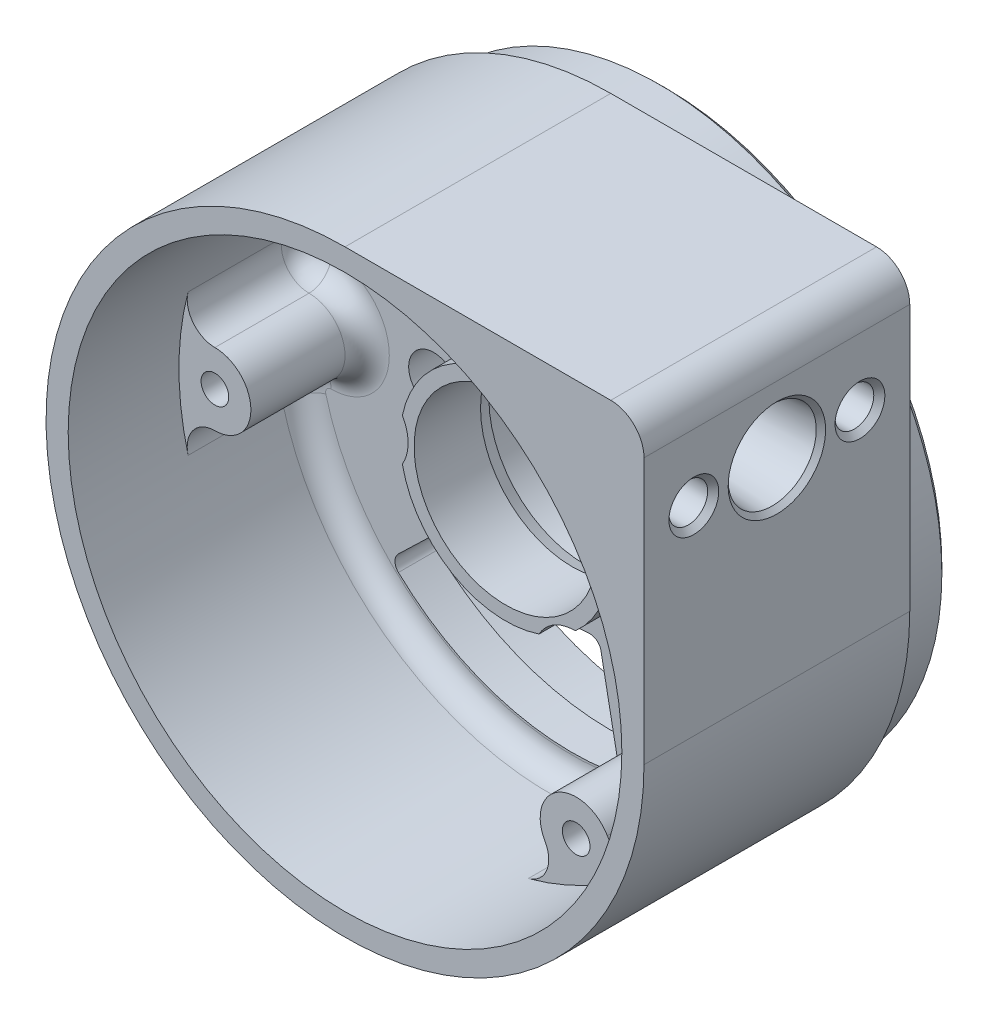
SolidWorks part; units mm, degrees
ref_plane "Front Plane" through (0, 0, 0) normal (0, 0, 1) x (1, 0, 0)
ref_plane "Top Plane" through (0, 0, 0) normal (0, 1, 0) x (1, 0, 0)
ref_plane "Right Plane" through (0, 0, 0) normal (1, 0, 0) x (0, 0, -1)
sketch "Sketch1" plane through (0, 0, 0) normal (0, 0, 1) x (1, 0, 0)
  line L0 (-12.5, 0) -> (0, 0) construction
  line L1 (0, 0) -> (6.25, 10.8253) construction
  line L2 (6.25, -10.8253) -> (0, 0) construction
  circle A0 centre (0, 0) radius 27
  circle A1 centre (0, 0) radius 12.5 construction
  circle A2 centre (0, 0) radius 7.75
  circle A3 centre (0, 0) radius 3 construction
  circle A4 centre (6.25, 10.8253) radius 2.25
  circle A5 centre (-12.5, 0) radius 2.25
  circle A6 centre (6.25, -10.8253) radius 2.25
  dimension "D1" = 54
  dimension "D2" = 6
  dimension "D3" = 15.5
  dimension "D4" = 25
  dimension "D7" = 4.5
  dimension "D5" = 120
  dimension "D6" = 120
extrude "Boss-Extrude1" add sketch "Sketch1" along normal blind 20
sketch "Sketch2" plane through (0, 0, 20) normal (0, 0, 1) x (1, 0, 0)
  circle A0 centre (6.25, 10.8253) radius 3.75
  circle A1 centre (6.25, -10.8253) radius 3.75
  circle A2 centre (-12.5, 0) radius 3.75
  dimension "D1" = 7.5
extrude "Cut-Extrude1" cut sketch "Sketch2" against normal offset from surface (15.5 mm away) 4.5 up to face at (27, 0, 0)
sketch "Sketch3" plane through (0, 0, 20) normal (0, 0, 1) x (1, 0, 0)
  line L0 (13.9654, 0) -> (0, 13.9654) construction
  line L1 (0, -17.6777) -> (17.6777, 0) construction
  line L2 (0, -17.6777) -> (-17.6777, 0) construction
  line L3 (-17.6777, 0) -> (0, 17.6777) construction
  line L4 (17.6777, 0) -> (0, 17.6777) construction
  line L5 (0, -17.6777) -> (0, 17.6777) construction
  line L6 (-17.6777, 0) -> (17.6777, 0) construction
  line L7 (0, 13.9654) -> (-13.9654, 0) construction
  line L8 (-13.9654, 0) -> (0, -13.9654) construction
  line L9 (0, -13.9654) -> (13.9654, 0) construction
  line L10 (-17.9605, 0) -> (0, 17.9605)
  line L11 (17.9605, 0) -> (0, 17.9605)
  line L12 (0, -17.9605) -> (17.9605, 0)
  line L13 (0, -17.9605) -> (-17.9605, 0)
  circle A0 centre (13.9654, 0) radius 1.625 construction
  circle A1 centre (0, -13.9654) radius 1.625 construction
  circle A2 centre (-13.9654, 0) radius 1.625 construction
  circle A3 centre (0, 13.9654) radius 1.625 construction
  point P0 (0, 0)
  dimension "D2" = 3.25
  dimension "D3" = 1
  dimension "D1" = 25
  dimension "D4" = 0.2
sketch "Sketch5" plane through (0, 0, 20) normal (0, 0, 1) x (1, 0, 0)
  line L0 (0, 27) -> (24, 27)
  line L3 (27, 0) -> (27, 24)
  circle A0 centre (0, 0) radius 27 construction
  arc A1 (0, 27) -> (27, 0) centre (0, 0) cw
  arc A3 (24, 27) -> (27, 24) centre (24, 24) cw
  circle M11 centre (0, 0) radius 27
extrude "Boss-Extrude2" add sketch "Sketch5" against normal up to surface (20 mm away) contours A3 L0 M11 | M11 region at (20.9021, 20.9021, 20) up to face at (27, 0, 0)
sketch "Sketch8" plane through (0, 0, 0) normal (0, 0, -1) x (-1, 0, 0)
  circle A0 centre (0, 0) radius 8.625
  dimension "D1" = 17.25
extrude "Cut-Extrude5" cut sketch "Sketch8" against normal blind 2
chamfer "Chamfer2" distance 1 angle 72 1 edges at (-7.75, 0, 2) first distance on face at (-7.75, 0, 2)
sketch "Sketch9" plane through (0, 0, 20) normal (0, 0, 1) x (1, 0, 0)
  circle A0 centre (0, 0) radius 25
  dimension "D1" = 50
extrude "Cut-Extrude6" cut sketch "Sketch9" against normal offset from surface (16.5 mm away) 3.5 up to face at (-8.625, 0, 0)
sketch "Sketch10" plane through (0, 0, 3.5) normal (0, 0, 1) x (1, 0, 0)
  line L0 (0, 0) -> (11.1505, 11.1233) construction
  line L1 (0, 0) -> (4.0578, -15.2183) construction
  line L2 (0, 0) -> (-15.2083, 4.095) construction
  line L3 (0, 0) -> (-2.716, 15.5141) construction
  line L4 (0, 0) -> (-12.0776, -10.1091) construction
  line L5 (0, 0) -> (13.8224, -5.0501) construction
  line L6 (-14.21, 3.8262) -> (-12.2736, 3.3048)
  line L7 (-2.1919, 12.5203) -> (-2.5377, 14.4956)
  line L8 (10.4185, 10.3931) -> (8.9988, 8.9768)
  line L9 (11.9388, -4.3619) -> (14.7936, -5.4049)
  line L10 (3.7914, -14.2193) -> (3.2748, -12.2816)
  line L11 (-9.747, -8.1584) -> (-11.2847, -9.4455)
  circle A0 centre (0, 0) radius 15.75 construction
  circle A1 centre (0, 0) radius 11.75 construction
  circle A2 centre (6.25, 10.8253) radius 2.25 construction
  arc A3 (-1.6579, 15.6625) -> (10.3708, 11.8537) centre (0, 0) cw
  arc A4 (14.3931, -6.3954) -> (5.0802, -14.9082) centre (0, 0) cw
  arc A5 (-15.451, 3.0545) -> (-12.7351, -9.2671) centre (0, 0) ccw
  arc A6 (-11.0713, 3.9355) -> (-2.9277, 11.3794) centre (0, 0) cw
  arc A7 (8.9439, 7.6203) -> (11.3187, -3.1542) centre (0, 0) cw
  arc A8 (2.1275, -11.5558) -> (-8.391, -8.2252) centre (0, 0) cw
  arc A9 (-8.391, -8.2252) -> (-9.747, -8.1584) centre (-9.1051, -8.9252) ccw
  arc A10 (2.1275, -11.5558) -> (3.2748, -12.2816) centre (2.3085, -12.5393) cw
  arc A11 (3.7914, -14.2193) -> (5.0802, -14.9082) centre (4.7577, -13.9616) ccw
  arc A12 (11.3187, -3.1542) -> (11.9388, -4.3619) centre (12.282, -3.4227) ccw
  arc A13 (14.3931, -6.3954) -> (13.8224, -5.0501) centre (13.4792, -5.9894) ccw
  arc A14 (8.9439, 7.6203) -> (8.9988, 8.9768) centre (9.7051, 8.2689) cw
  arc A15 (10.4185, 10.3931) -> (10.3708, 11.8537) centre (9.7123, 11.1011) ccw
  arc A16 (-2.5377, 14.4956) -> (-1.6579, 15.6625) centre (-1.5527, 14.6681) cw
  arc A17 (-2.9277, 11.3794) -> (-2.1919, 12.5203) centre (-3.1769, 12.3479) ccw
  arc A18 (-11.0713, 3.9355) -> (-12.2736, 3.3048) centre (-12.0136, 4.2704) cw
  arc A19 (-14.21, 3.8262) -> (-15.451, 3.0545) centre (-14.47, 2.8606) ccw
  arc A20 (-12.7351, -9.2671) -> (-11.2847, -9.4455) centre (-11.9266, -8.6787) ccw
  point P23 (-9.0103, -7.5417)
  point P26 (3.0272, -11.3533)
  point P31 (11.0365, -4.0322)
  point P37 (8.3187, 8.2983)
  point P46 (-2.0262, 11.574)
  point P49 (-11.3459, 3.055)
  dimension "D1" = 23.5
  dimension "D2" = 31.5
  dimension "D6" = 55
  dimension "D9" = 1
  dimension "D3" = 120
  dimension "D4" = 120
  dimension "D5" = 1
  dimension "D7" = 55
  dimension "D8" = 55
sketch "Sketch11" plane through (0, 0, 3.5) normal (0, 0, 1) x (1, 0, 0)
  line L0 (-3.3134, 13.3589) -> (-5.2425, 21.1366)
  line L1 (-13.0084, 4.4969) -> (-20.5819, 7.1151)
  line L2 (10.3986, 9.0171) -> (16.4528, 14.2669)
  line L3 (-14.21, 3.8262) -> (-12.2736, 3.3048) construction
  line L4 (-2.1919, 12.5203) -> (-2.5377, 14.4956) construction
  line L5 (13.2259, -3.81) -> (20.9261, -6.0282)
  line L6 (2.6097, -13.514) -> (4.1291, -21.382)
  line L7 (-9.9125, -9.549) -> (-15.6836, -15.1084)
  line L8 (0, 0) -> (-3.9736, 12.1676) construction
  line L9 (0, 0) -> (12.5242, -2.6426) construction
  arc A0 (-3.9736, 12.1676) -> (-11.7627, 5.0477) centre (0, 0) ccw
  circle A1 centre (0, 0) radius 25 construction
  arc A2 (-21.1843, 8.4299) -> (-20.5819, 7.1151) centre (-20.2552, 8.0602) ccw
  arc A3 (-6.4981, 21.8544) -> (-21.1843, 8.4299) centre (0, 0) ccw
  arc A4 (-11.7627, 5.0477) -> (-13.0084, 4.4969) centre (-12.6816, 5.4421) cw
  arc A5 (-3.9736, 12.1676) -> (-3.3134, 13.3589) centre (-4.284, 13.1182) ccw
  arc A6 (-5.2425, 21.1366) -> (-6.4981, 21.8544) centre (-6.2131, 20.8959) ccw
  arc A7 (10.2528, 7.6629) -> (10.3986, 9.0171) centre (11.0538, 8.2616) cw
  arc A8 (17.8927, 14.1312) -> (16.4528, 14.2669) centre (17.1079, 13.5114) ccw
  arc A9 (22.1755, -5.2997) -> (17.8927, 14.1312) centre (0, 0) ccw
  arc A10 (20.9261, -6.0282) -> (22.1755, -5.2997) centre (21.2029, -5.0672) ccw
  arc A11 (12.5242, -2.6426) -> (13.2259, -3.81) centre (13.5027, -2.849) ccw
  arc A12 (12.5242, -2.6426) -> (10.2528, 7.6629) centre (0, 0) ccw
  arc A13 (1.5099, -12.7106) -> (2.6097, -13.514) centre (1.6279, -13.7037) cw
  arc A14 (3.2916, -22.5611) -> (4.1291, -21.382) centre (3.1473, -21.5716) ccw
  arc A15 (-15.6774, -16.5547) -> (3.2916, -22.5611) centre (0, 0) ccw
  arc A16 (-15.6836, -15.1084) -> (-15.6774, -16.5547) centre (-14.9898, -15.8286) ccw
  arc A17 (-8.5507, -9.525) -> (-9.9125, -9.549) centre (-9.2187, -10.2692) ccw
  arc A18 (-8.5507, -9.525) -> (1.5099, -12.7106) centre (0, 0) ccw
  dimension "D3" = 10
  dimension "D4" = 2.2
  dimension "D5" = 1
  dimension "D1" = 4
  dimension "D2" = 4
  dimension "D6" = 120
extrude "Cut-Extrude7" cut sketch "Sketch11" against normal through all
sketch "Sketch13" plane through (0, 0, 0) normal (0, 0, -1) x (-1, 0, 0)
  circle A0 centre (0, 0) radius 24.2
  arc A1 (-27, 0) -> (0, 27) centre (0, 0) ccw construction
  circle A2 centre (0, 0) radius 25.5
  dimension "D1" = 2.8
  dimension "D2" = 1.5
extrude "Boss-Extrude3" add sketch "Sketch13" along normal blind 5
fillet "Fillet2" radius 1 1 edges at (-24.2, 0, 0)
chamfer "Chamfer3" distance 0.6 angle 45 1 edges at (-25.5, 0, -5)
sketch "Sketch14" plane through (0, 0, 3.5) normal (0, 0, 1) x (1, 0, 0)
  line L0 (0, 0) -> (-25, 0) construction
  line L1 (0, 0) -> (12.5, 21.6506) construction
  line L2 (0, 0) -> (12.5, -21.6506) construction
  circle A0 centre (0, 0) radius 25 construction
  circle A1 centre (0, 0) radius 25 construction
  circle A2 centre (6.25, -10.8253) radius 2.25 construction
  circle A3 centre (6.25, -10.8253) radius 2.25 construction
  circle A4 centre (6.25, 10.8253) radius 2.25 construction
  circle A5 centre (-12.5, 0) radius 2.25 construction
  circle A6 centre (6.25, 10.8253) radius 2.25 construction
  circle A7 centre (-12.5, 0) radius 2.25 construction
  circle A8 centre (-21.75, 0) radius 3.25 construction
  arc A9 (-21.75, 3.25) -> (-24.169, 6.392) centre (-21.75, 5.7522) cw
  arc A10 (-21.75, -3.25) -> (-24.169, -6.392) centre (-21.75, -5.7522) ccw
  arc A11 (-21.75, 3.25) -> (-21.75, -3.25) centre (-21.75, 0) cw
  arc A12 (-24.169, 6.392) -> (-24.169, -6.392) centre (0, 0) ccw
  arc A13 (13.6896, 17.2111) -> (17.6201, 17.735) centre (15.8566, 15.9599) cw
  arc A14 (8.0604, 20.4611) -> (6.5489, 24.127) centre (5.8934, 21.7122) ccw
  arc A15 (13.6896, 17.2111) -> (8.0604, 20.4611) centre (10.875, 18.8361) cw
  arc A16 (17.6201, 17.735) -> (6.5489, 24.127) centre (0, 0) ccw
  circle A17 centre (10.875, 18.8361) radius 3.25 construction
  arc A18 (8.0604, -20.4611) -> (6.5489, -24.127) centre (5.8934, -21.7122) cw
  arc A19 (13.6896, -17.2111) -> (17.6201, -17.735) centre (15.8566, -15.9599) ccw
  arc A20 (8.0604, -20.4611) -> (13.6896, -17.2111) centre (10.875, -18.8361) cw
  arc A21 (6.5489, -24.127) -> (17.6201, -17.735) centre (0, 0) ccw
  circle A22 centre (10.875, -18.8361) radius 3.25 construction
  circle A23 centre (-21.75, 0) radius 1.25
  circle A24 centre (10.875, -18.8361) radius 1.25
  circle A25 centre (10.875, 18.8361) radius 1.25
  point P49 (0, 0)
  dimension "D1" = 6.5
  dimension "D3" = 2.5
  dimension "D2" = 3
extrude "Boss-Extrude4" add sketch "Sketch14" along normal offset from surface (10.5 mm away) 6 up to face at (25, 0, 20)
fillet "Fillet4" radius 2 12 edges at (8.2067, 22.666, 3.5) (-12.5, 21.6506, 3.5) (-23.7327, 4.2257, 3.5) (-18.5, 0, 3.5) (-23.7327, -4.2257, 3.5) (-12.5, -21.6506, 3.5) (8.2067, -22.666, 3.5) (9.25, -16.0215, 3.5) (15.5259, -18.4402, 3.5) (25, 0, 3.5) (15.5259, 18.4402, 3.5) (9.25, 16.0215, 3.5)
sketch "Sketch16" plane through (0, 0, 20) normal (0, 0, 1) x (1, 0, 0)
  line L2 (27, 0) -> (27, 24)
  line L3 (24, 27) -> (0, 27)
  line L4 (27, 0) -> (27, 24)
  line L5 (24, 27) -> (0, 27)
  circle A0 centre (0, 0) radius 25 construction
  circle A1 centre (0, 0) radius 25
  arc A2 (0, 27) -> (27, 0) centre (0, 0) ccw
  arc A3 (27, 24) -> (24, 27) centre (24, 24) ccw
  arc A4 (0, 27) -> (27, 0) centre (0, 0) ccw
  arc A5 (27, 24) -> (24, 27) centre (24, 24) ccw
  dimension "D1" = 0
extrude "Boss-Extrude5" add sketch "Sketch16" along normal blind 4
sketch "Sketch6" plane through (27, 0, 0) normal (1, 0, 0) x (0, 0, -1)
  line L0 (-12, 27) -> (-12, -27) construction
  line L3 (0, 27) -> (-24, 27) construction
  line L5 (-24, -27) -> (0, -27) construction
  circle A0 centre (-12, 18) radius 4
  dimension "D1" = 8
  dimension "D2" = 9
extrude "Cut-Extrude4" cut sketch "Sketch6" against normal blind 6 draft 3
fillet "Fillet3" radius 1 1 edges at (25.5, 0, 0)
sketch "Sketch17" plane through (27, 0, 0) normal (1, 0, 0) x (0, 0, -1)
  line L0 (-24, 18) -> (0, 18) construction
  line L1 (-24, 0) -> (-24, 24) construction
  line L2 (0, 24) -> (0, 0) construction
  line L3 (-19.5, 18) -> (-4.5, 18) construction
  circle A2 centre (-12, 18) radius 4 construction
  circle A3 centre (-12, 18) radius 4 construction
  circle A4 centre (-19.5, 18) radius 1.75
  circle A5 centre (-4.5, 18) radius 1.75
  point P13 (-12, 18)
  dimension "D1" = 3.5
  dimension "D2" = 15
extrude "Cut-Extrude8" cut sketch "Sketch17" against normal blind 5
chamfer "Chamfer4" distance 1 angle 45 2 edges at (22, 19.75, 4.5) (22, 19.75, 19.5)
chamfer "Chamfer5" distance 0.5 angle 45 2 edges at (27, 19.75, 19.5) (27, 19.75, 4.5)
chamfer "Chamfer6" distance 0.4 angle 45 1 edges at (27, 22, 12) first distance on face at (27, 20.25, 19.5)
sketch "Sketch18" plane through (0, 0, 3.5) normal (0, 0, 1) x (1, 0, 0)
  circle A0 centre (0, 0) radius 8.2626 construction
  circle A1 centre (0, 0) radius 8.2626
  circle A2 centre (0, 0) radius 9.5126 construction
  circle A3 centre (-12.5, 0) radius 3.7 construction
  circle A4 centre (6.25, -10.8253) radius 3.7 construction
  circle A5 centre (6.25, 10.8253) radius 3.7 construction
  arc A6 (-9.322, -1.8948) -> (3.02, -9.0205) centre (0, 0) ccw
  arc A7 (-9.322, -1.8948) -> (-9.322, 1.8948) centre (-12.5, 0) ccw
  arc A8 (-9.322, 1.8948) -> (3.02, 9.0205) centre (0, 0) cw
  arc A9 (3.02, 9.0205) -> (6.302, 7.1257) centre (6.25, 10.8253) ccw
  arc A10 (6.302, 7.1257) -> (6.302, -7.1257) centre (0, 0) cw
  arc A11 (6.302, -7.1257) -> (3.02, -9.0205) centre (6.25, -10.8253) ccw
  point P20 (3.0278, -9.0068)
  dimension "D1" = 1.25
  dimension "D2" = 7.4
extrude "Boss-Extrude6" add sketch "Sketch18" along normal blind 6
fillet "Fillet5" radius 1.5 3 edges at (9.5126, 0, 3.5) (-4.7563, 8.2382, 3.5) (-4.7563, -8.2382, 3.5)
sketch "Sketch20" plane through (0, 0, 3.5) normal (0, 0, 1) x (1, 0, 0)
  circle A0 centre (0, 0) radius 25 construction
  circle A1 centre (0, 0) radius 25
extrude "Boss-Extrude7" [suppressed] add sketch "Sketch20" against normal blind 0.2
sketch "Sketch19" plane through (0, 0, 14) normal (0, 0, 1) x (1, 0, 0)
  circle A0 centre (-21.75, 0) radius 1.25 construction
  circle A1 centre (10.875, -18.8361) radius 1.25 construction
  circle A2 centre (10.875, 18.8361) radius 1.25 construction
  circle A3 centre (-21.75, 0) radius 1.25
  circle A4 centre (10.875, -18.8361) radius 1.25
  circle A5 centre (10.875, 18.8361) radius 1.25
extrude "Cut-Extrude9" cut sketch "Sketch19" against normal through all
